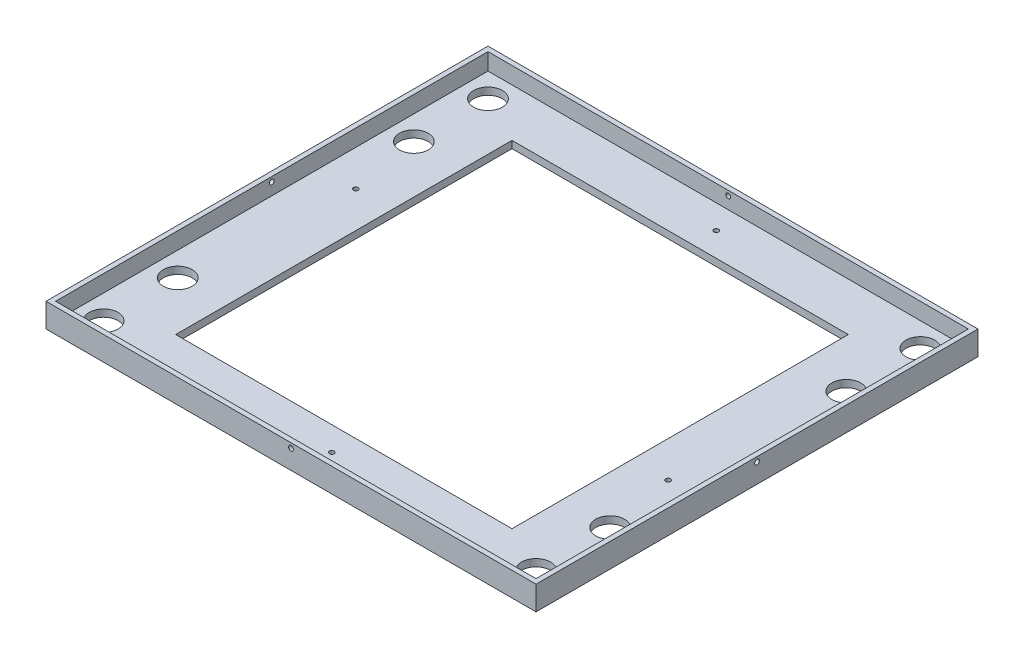
SolidWorks part; units mm, degrees
ref_plane "Front Plane" through (0, 0, 0) normal (0, 0, 1) x (1, 0, 0)
ref_plane "Top Plane" through (0, 0, 0) normal (0, 1, 0) x (1, 0, 0)
ref_plane "Right Plane" through (0, 0, 0) normal (1, 0, 0) x (0, 0, -1)
sketch "Sketch1" plane through (0, 0, 0) normal (0, 1, 0) x (1, 0, 0)
  line L0 (-100, 0) -> (100, 0) construction
  line L1 (-100, 90) -> (100, 90)
  line L2 (-100, 90) -> (-100, -90)
  line L3 (-100, -90) -> (100, -90)
  line L4 (100, 90) -> (100, -90)
  line L5 (-100, 90) -> (100, -90) construction
  line L6 (-100, -90) -> (100, 90) construction
  line L7 (0, 90) -> (0, -90) construction
  line L8 (-70, 70) -> (70, 70)
  line L9 (-70, 70) -> (-70, -70)
  line L10 (-70, -70) -> (70, -70)
  line L11 (70, 70) -> (70, -70)
  line L12 (-70, 70) -> (70, -70) construction
  line L13 (-70, -70) -> (70, 70) construction
  line L19 (-102, -92) -> (102, 92) construction
  line L20 (-102, 92) -> (102, -92) construction
  line L21 (102, 92) -> (-102, 92)
  line L22 (102, 92) -> (102, -92)
  line L23 (102, -92) -> (-102, -92)
  line L24 (-102, 92) -> (-102, -92)
  line L25 (102, 92) -> (-102, -92) construction
  line L26 (102, -92) -> (-102, 92) construction
  circle A0 centre (5, 80) radius 1
  circle A1 centre (5, -80) radius 1
  circle A2 centre (-85, 20) radius 1
  circle A3 centre (-90, 80) radius 6
  circle A4 centre (-90, 49.146) radius 6
  circle A5 centre (-90, -80) radius 6
  circle A6 centre (-90, -49.146) radius 6
  circle A7 centre (90, -80) radius 6
  circle A8 centre (90, -49.146) radius 6
  circle A9 centre (90, 49.146) radius 6
  circle A10 centre (90, 80) radius 6
  circle A11 centre (85, -20) radius 1
  point P0 (0, 0)
  point P14 (0, 0)
  point P39 (0, 0)
  point P40 (0, 0)
  dimension "D1" = 95
  dimension "D3" = 70
  dimension "D5" = 10
  dimension "D7" = 200
  dimension "D9" = 70
  dimension "D2" = 10
  dimension "D4" = 15
  dimension "D6" = 10
  dimension "D8" = 180
  dimension "D10" = 15
  dimension "D11" = 10
extrude "Boss-Extrude4" add sketch "Sketch1" along normal blind 3 contours L4 L1 L2 L3 A11 A9 A8 A7 A5 A4 A3 A2 L8 L11 L10 L9 A0 A1 A6 A10 region at (0, 0, -87.3093)
extrude "Boss-Extrude5" add sketch "Sketch1<3>" along normal blind 10 contours L21 L24 L23 L22 L1 L4 L3 L2 region at (101.7253, 0, 0)
sketch "Sketch1<3>" plane through (0, 0, 0) normal (0, 1, 0) x (1, 0, 0) same geometry as "Sketch1"
sketch "Sketch4" plane through (-102, 0, 0) normal (-1, 0, 0) x (0, 0, 1)
  line L0 (-92, 0) -> (92, 0) construction
  circle A0 centre (0, 8) radius 1
  dimension "D1" = 8
sketch "Sketch5" plane through (0, 0, 92) normal (0, 0, 1) x (1, 0, 0)
  line L0 (102, 0) -> (-102, 0) construction
  circle A0 centre (0, 8) radius 1
  point P2 (0, 0)
  dimension "D1" = 8
sketch "Sketch6" plane through (102, 0, 0) normal (1, 0, 0) x (0, 0, -1)
  line L0 (92, 0) -> (-92, 0) construction
  circle A0 centre (0, 8) radius 1
  dimension "D1" = 8
sketch "Sketch7" plane through (0, 0, -92) normal (0, 0, -1) x (-1, 0, 0)
  line L0 (-102, 0) -> (102, 0) construction
  circle A0 centre (0, 8) radius 1
  dimension "D1" = 8
extrude "Cut-Extrude1" cut sketch "Sketch4" against normal blind 2
extrude "Cut-Extrude2" cut sketch "Sketch7" against normal blind 2
extrude "Cut-Extrude3" cut sketch "Sketch6" against normal blind 2
extrude "Cut-Extrude4" cut sketch "Sketch5" against normal blind 2
